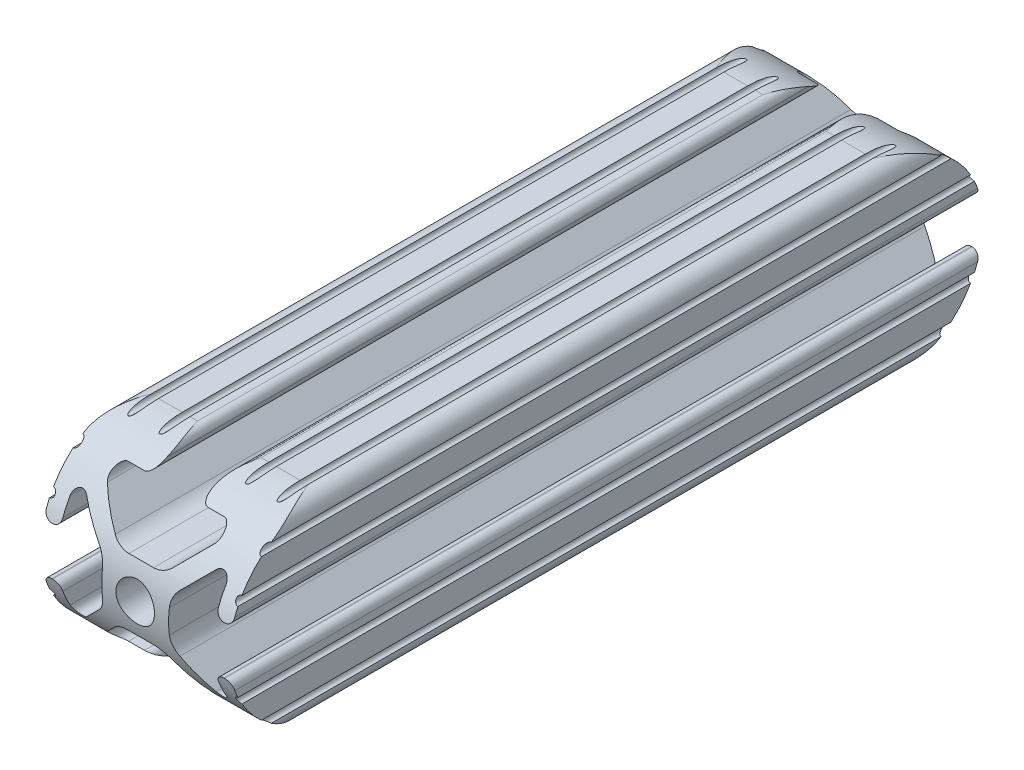
SolidWorks part; units mm, degrees
ref_plane "Front Plane" through (0, 0, 0) normal (0, 0, 1) x (1, 0, 0)
ref_plane "Top Plane" through (0, 0, 0) normal (0, 1, 0) x (1, 0, 0)
ref_plane "Right Plane" through (0, 0, 0) normal (1, 0, 0) x (0, 0, -1)
sketch "Sketch1" plane through (0, 0, 0) normal (0, 0, 1) x (1, 0, 0)
  line L88 (-7.1797, -8.6452) -> (-3.9523, -5.4237)
  line L89 (-1.7093, -4.4958) -> (1.7093, -4.4958)
  line L90 (3.9523, -5.4237) -> (7.1797, -8.6452)
  line L91 (6.4164, -10.4902) -> (4.2875, -10.4902)
  line L92 (3.2385, -11.5392) -> (3.2385, -11.651)
  line L93 (4.2875, -12.7) -> (5.3171, -12.7)
  line L94 (6.3331, -12.7) -> (9.5504, -12.7)
  line L95 (12.7, -9.5504) -> (12.7, -6.3331)
  line L96 (12.7, -5.3171) -> (12.7, -4.2875)
  line L97 (11.651, -3.2385) -> (11.5392, -3.2385)
  line L98 (10.4902, -4.2875) -> (10.4902, -6.4021)
  line L99 (8.7371, -7.1294) -> (5.441, -3.8408)
  line L100 (4.5085, -1.5932) -> (4.5085, 1.5932)
  line L101 (5.441, 3.8408) -> (8.7371, 7.1294)
  line L102 (10.4902, 6.4021) -> (10.4902, 4.2875)
  line L103 (11.5392, 3.2385) -> (11.651, 3.2385)
  line L104 (12.7, 4.2875) -> (12.7, 5.3171)
  line L105 (12.7, 6.3331) -> (12.7, 9.5504)
  line L106 (9.5504, 12.7) -> (6.3331, 12.7)
  line L107 (5.3171, 12.7) -> (4.2875, 12.7)
  line L108 (3.2385, 11.651) -> (3.2385, 11.5392)
  line L109 (4.2875, 10.4902) -> (6.4768, 10.4902)
  line L110 (7.207, 8.7244) -> (3.8983, 5.4232)
  line L111 (1.6558, 4.4958) -> (-1.6558, 4.4958)
  line L112 (-3.8983, 5.4232) -> (-7.207, 8.7244)
  line L113 (-6.4768, 10.4902) -> (-4.2875, 10.4902)
  line L114 (-3.2385, 11.5392) -> (-3.2385, 11.651)
  line L115 (-4.2875, 12.7) -> (-5.3171, 12.7)
  line L116 (-6.3331, 12.7) -> (-9.5504, 12.7)
  line L117 (-12.7, 9.5504) -> (-12.7, 6.3331)
  line L118 (-12.7, 5.3171) -> (-12.7, 4.2875)
  line L119 (-11.651, 3.2385) -> (-11.5392, 3.2385)
  line L120 (-10.4902, 4.2875) -> (-10.4902, 6.4021)
  line L121 (-8.7371, 7.1294) -> (-5.441, 3.8408)
  line L122 (-4.5085, 1.5932) -> (-4.5085, -1.5932)
  line L123 (-5.441, -3.8408) -> (-8.7371, -7.1294)
  line L124 (-10.4902, -6.4021) -> (-10.4902, -4.2875)
  line L125 (-11.5392, -3.2385) -> (-11.651, -3.2385)
  line L126 (-12.7, -4.2875) -> (-12.7, -5.3171)
  line L127 (-12.7, -6.3331) -> (-12.7, -9.5504)
  line L128 (-9.5504, -12.7) -> (-6.3331, -12.7)
  line L129 (-5.3171, -12.7) -> (-4.2875, -12.7)
  line L130 (-3.2385, -11.651) -> (-3.2385, -11.5392)
  line L131 (-4.2875, -10.4902) -> (-6.4164, -10.4902)
  circle A1 centre (0, 0) radius 2.6035
  arc A104 (-7.1797, -8.6452) -> (-6.4164, -10.4902) centre (-6.4164, -9.4098) ccw
  arc A105 (-1.7093, -4.4958) -> (-3.9523, -5.4237) centre (-1.7093, -7.6708) ccw
  arc A106 (3.9523, -5.4237) -> (1.7093, -4.4958) centre (1.7093, -7.6708) ccw
  arc A107 (6.4164, -10.4902) -> (7.1797, -8.6452) centre (6.4164, -9.4098) ccw
  arc A108 (4.2875, -10.4902) -> (3.2385, -11.5392) centre (4.2875, -11.5392) ccw
  arc A109 (3.2385, -11.651) -> (4.2875, -12.7) centre (4.2875, -11.651) ccw
  arc A110 (6.3331, -12.7) -> (5.3171, -12.7) centre (5.8251, -12.7) ccw
  arc A111 (10.5664, -12.6998) -> (9.5504, -12.7) centre (10.0584, -12.7) ccw
  arc A112 (10.5664, -12.6998) -> (12.6998, -10.5664) centre (10.5918, -10.5918) ccw
  arc A113 (12.7, -9.5504) -> (12.6998, -10.5664) centre (12.7, -10.0584) ccw
  arc A114 (12.7, -5.3171) -> (12.7, -6.3331) centre (12.7, -5.8251) ccw
  arc A115 (12.7, -4.2875) -> (11.651, -3.2385) centre (11.651, -4.2875) ccw
  arc A116 (11.5392, -3.2385) -> (10.4902, -4.2875) centre (11.5392, -4.2875) ccw
  arc A117 (8.7371, -7.1294) -> (10.4902, -6.4021) centre (9.4628, -6.4021) ccw
  arc A118 (4.5085, -1.5932) -> (5.441, -3.8408) centre (7.6835, -1.5932) ccw
  arc A119 (5.441, 3.8408) -> (4.5085, 1.5932) centre (7.6835, 1.5932) ccw
  arc A120 (10.4902, 6.4021) -> (8.7371, 7.1294) centre (9.4628, 6.4021) ccw
  arc A121 (10.4902, 4.2875) -> (11.5392, 3.2385) centre (11.5392, 4.2875) ccw
  arc A122 (11.651, 3.2385) -> (12.7, 4.2875) centre (11.651, 4.2875) ccw
  arc A123 (12.7, 6.3331) -> (12.7, 5.3171) centre (12.7, 5.8251) ccw
  arc A124 (12.6998, 10.5664) -> (12.7, 9.5504) centre (12.7, 10.0584) ccw
  arc A125 (12.6998, 10.5664) -> (10.5664, 12.6998) centre (10.5918, 10.5918) ccw
  arc A126 (9.5504, 12.7) -> (10.5664, 12.6998) centre (10.0584, 12.7) ccw
  arc A127 (5.3171, 12.7) -> (6.3331, 12.7) centre (5.8251, 12.7) ccw
  arc A128 (4.2875, 12.7) -> (3.2385, 11.651) centre (4.2875, 11.651) ccw
  arc A129 (3.2385, 11.5392) -> (4.2875, 10.4902) centre (4.2875, 11.5392) ccw
  arc A130 (7.207, 8.7244) -> (6.4768, 10.4902) centre (6.4768, 9.4563) ccw
  arc A131 (1.6558, 4.4958) -> (3.8983, 5.4232) centre (1.6558, 7.6708) ccw
  arc A132 (-3.8983, 5.4232) -> (-1.6558, 4.4958) centre (-1.6558, 7.6708) ccw
  arc A133 (-6.4768, 10.4902) -> (-7.207, 8.7244) centre (-6.4768, 9.4563) ccw
  arc A134 (-4.2875, 10.4902) -> (-3.2385, 11.5392) centre (-4.2875, 11.5392) ccw
  arc A135 (-3.2385, 11.651) -> (-4.2875, 12.7) centre (-4.2875, 11.651) ccw
  arc A136 (-6.3331, 12.7) -> (-5.3171, 12.7) centre (-5.8251, 12.7) ccw
  arc A137 (-10.5664, 12.6998) -> (-9.5504, 12.7) centre (-10.0584, 12.7) ccw
  arc A138 (-10.5664, 12.6998) -> (-12.6998, 10.5664) centre (-10.5918, 10.5918) ccw
  arc A139 (-12.7, 9.5504) -> (-12.6998, 10.5664) centre (-12.7, 10.0584) ccw
  arc A140 (-12.7, 5.3171) -> (-12.7, 6.3331) centre (-12.7, 5.8251) ccw
  arc A141 (-12.7, 4.2875) -> (-11.651, 3.2385) centre (-11.651, 4.2875) ccw
  arc A142 (-11.5392, 3.2385) -> (-10.4902, 4.2875) centre (-11.5392, 4.2875) ccw
  arc A143 (-8.7371, 7.1294) -> (-10.4902, 6.4021) centre (-9.4628, 6.4021) ccw
  arc A144 (-4.5085, 1.5932) -> (-5.441, 3.8408) centre (-7.6835, 1.5932) ccw
  arc A145 (-5.441, -3.8408) -> (-4.5085, -1.5932) centre (-7.6835, -1.5932) ccw
  arc A146 (-10.4902, -6.4021) -> (-8.7371, -7.1294) centre (-9.4628, -6.4021) ccw
  arc A147 (-10.4902, -4.2875) -> (-11.5392, -3.2385) centre (-11.5392, -4.2875) ccw
  arc A148 (-11.651, -3.2385) -> (-12.7, -4.2875) centre (-11.651, -4.2875) ccw
  arc A149 (-12.7, -6.3331) -> (-12.7, -5.3171) centre (-12.7, -5.8251) ccw
  arc A150 (-12.6998, -10.5664) -> (-12.7, -9.5504) centre (-12.7, -10.0584) ccw
  arc A151 (-12.6998, -10.5664) -> (-10.5664, -12.6998) centre (-10.5918, -10.5918) ccw
  arc A152 (-9.5504, -12.7) -> (-10.5664, -12.6998) centre (-10.0584, -12.7) ccw
  arc A153 (-5.3171, -12.7) -> (-6.3331, -12.7) centre (-5.8251, -12.7) ccw
  arc A154 (-4.2875, -12.7) -> (-3.2385, -11.651) centre (-4.2875, -11.651) ccw
  arc A155 (-3.2385, -11.5392) -> (-4.2875, -10.4902) centre (-4.2875, -11.5392) ccw
extrude "Boss-Extrude1" add sketch "Sketch1" along normal mid plane 101.6
sketch "Sketch2" plane through (12.7, 0, 0) normal (1, 0, 0) x (0, 0, -1)
  line L0 (-50.8, 0) -> (50.8, 0) construction
  line L1 (50.8, -12.7) -> (-50.8, -12.7)
  line L2 (50.8, -12.7) -> (50.8, 12.7)
  line L3 (50.8, 12.7) -> (-50.8, 12.7)
  line L4 (-50.8, -12.7) -> (-50.8, 12.7)
  line L5 (50.8, -12.7) -> (-50.8, 12.7) construction
  line L6 (50.8, 12.7) -> (-50.8, -12.7) construction
  circle A0 centre (-38.1, 0) radius 12.7
  circle A1 centre (38.1, 0) radius 12.7
  circle A2 centre (-38.1, 0) radius 3.9687
  point P0 (0, 0)
  line M7 (50.8, -9.5504) -> (50.8, -6.3331)
  line M8 (50.8, -6.3331) -> (-50.8, -6.3331)
  line M9 (-50.8, -6.3331) -> (-50.8, -9.5504)
  line M10 (-50.8, -9.5504) -> (50.8, -9.5504)
  dimension "D1" = 7.9375
extrude "Cut-Extrude1" cut sketch "Sketch2" against normal through all contours A0 L3 L4 | A0 L4 M8 | A0 M8 M9 M10 | A0 L4 L1 M10 | A1 L1 L2 M10 | A1 M10 M7 M8 | A1 L2 M8 | A1 L2 L3 region at (12.7, -11.3727, -47.0456) region at (12.7, -8.1865, -49.2688) region at (12.7, -11.3727, 47.0456) region at (12.7, -4.7717, -50.2989) region at (12.7, -8.1865, 49.2688) region at (12.7, 9.8632, -47.9632) region at (12.7, -4.7717, 50.2989) region at (12.7, 9.8632, 47.9632)
